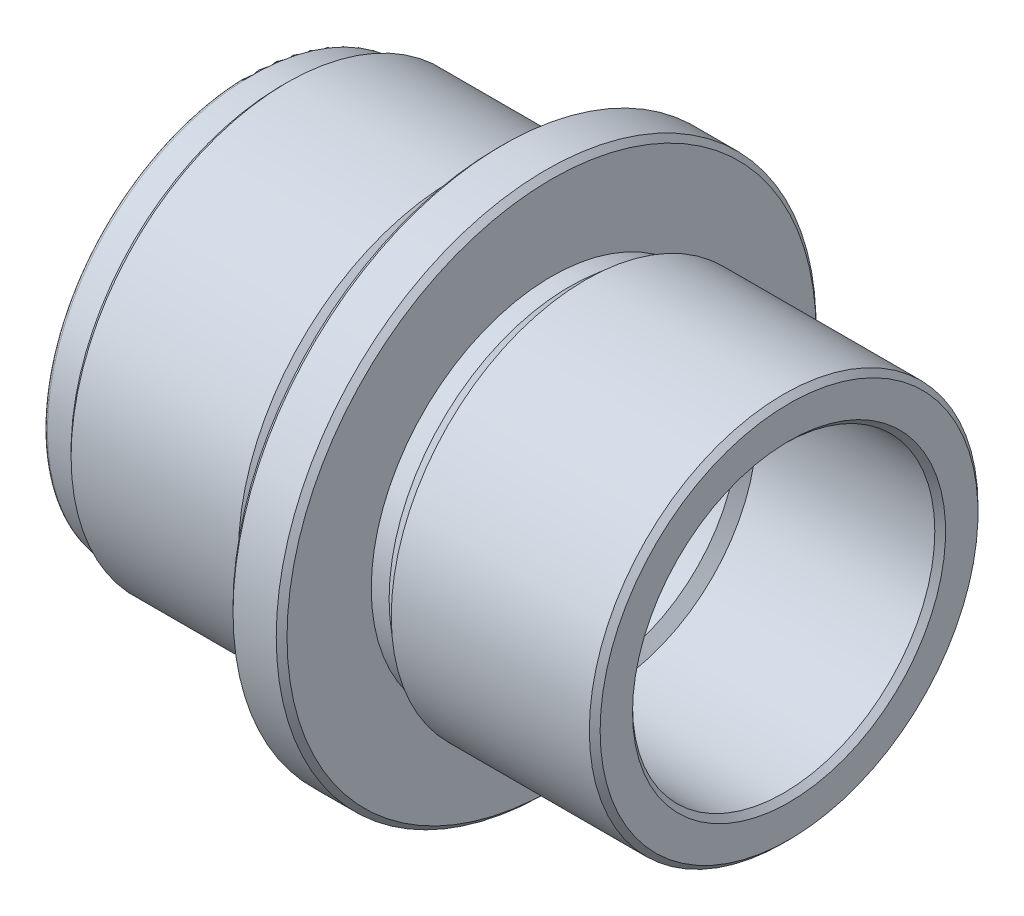
SolidWorks part; units mm, degrees
note: '?' marks a value the reader was unsure of.
ref_plane "Plane1" through (0, 0, 0) normal (0, 0, 1) x (1, 0, 0)
ref_plane "Plane2" through (0, 0, 0) normal (0, 1, 0) x (1, 0, 0)
ref_plane "Plane3" through (0, 0, 0) normal (1, 0, 0) x (0, 0, -1)
sketch "Sketch1" plane through (0, 0, 0) normal (0, 0, 1) x (1, 0, 0)
  line L0 (0, 35.56) -> (0, 48.26)
  line L1 (0, 48.26) -> (7.62, 48.26)
  line L2 (7.62, 48.26) -> (7.62, 50.8)
  line L3 (7.62, 50.8) -> (48.26, 50.8)
  line L4 (48.26, 50.8) -> (50.8, 48.26)
  line L5 (50.8, 48.26) -> (58.42, 48.26)
  line L6 (58.42, 48.26) -> (58.42, 63.5)
  line L7 (58.42, 63.5) -> (71.12, 63.5)
  line L8 (71.12, 63.5) -> (71.12, 42.4161)
  line L9 (71.12, 42.4161) -> (75.3191, 42.4161)
  line L10 (75.3191, 42.4161) -> (79.1291, 45.72)
  line L11 (79.1291, 45.72) -> (127, 45.72)
  line L12 (127, 45.72) -> (127, 35.56)
  line L13 (127, 35.56) -> (83.82, 35.56)
  line L14 (83.82, 35.56) -> (81.915, 33.02)
  line L15 (81.915, 33.02) -> (63.5, 33.02)
  line L16 (63.5, 33.02) -> (63.5, 30.48)
  line L17 (63.5, 30.48) -> (38.1, 30.48)
  line L18 (38.1, 30.48) -> (38.1, 38.1)
  line L19 (38.1, 38.1) -> (10.16, 38.1)
  line L20 (10.16, 38.1) -> (10.16, 35.56)
  line L21 (10.16, 35.56) -> (0, 35.56)
  line L22 (0, 0) -> (127, 0) construction
revolve "Base-Revolve" add sketch "Sketch1" angle 360 about L22
chamfer "Chamfer1" distance 1.27 angle 45
fillet "Fillet1" radius 0.762
ref_axis "Axis1" through (-50, 0, 0) along (1, 0, 0)?
sketch "Sketch6" plane through (0, 0, 0) normal (0, 0, 1) x (1, 0, 0)
  line L0 (0, 0) -> (1.27, 0) construction
  line L1 (-6.3418, 0) -> (132.08, 0)
  line L2 (-6.3418, 0) -> (-6.3418, 63.5)
  line L3 (-6.3418, 63.5) -> (132.08, 63.5)
  line L4 (132.08, 0) -> (132.08, 63.5)
